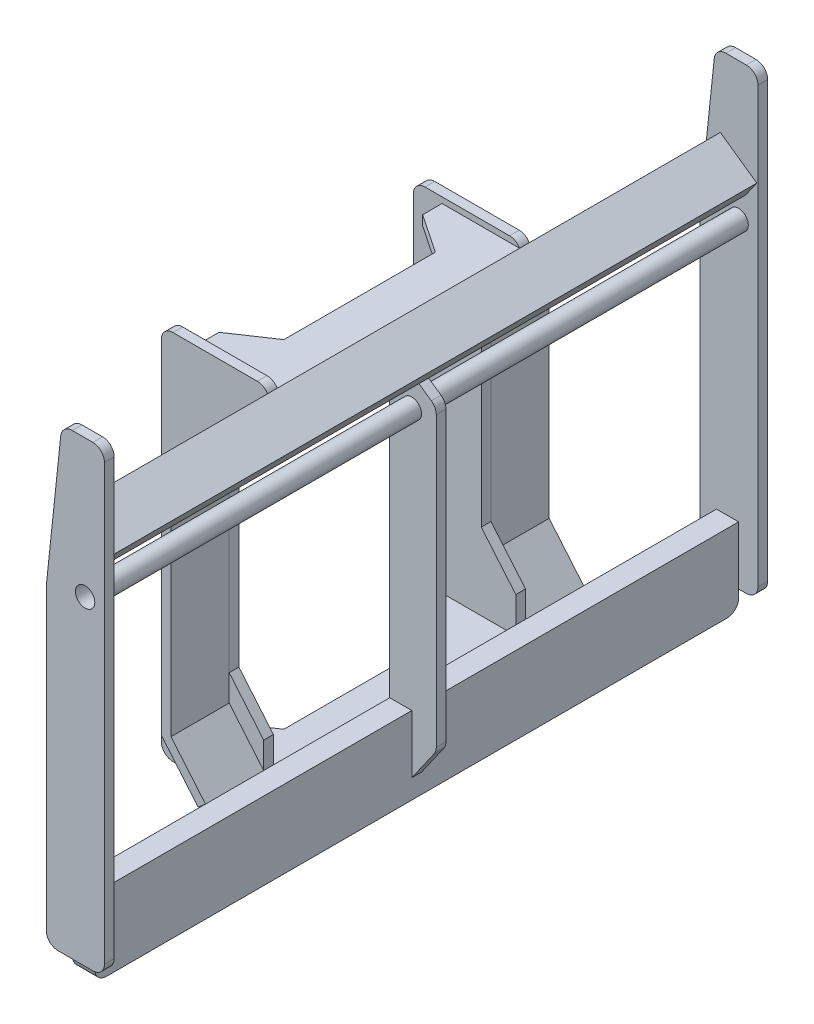
SolidWorks part; units mm, degrees
ref_plane "Front Plane" through (0, 0, 0) normal (0, 0, 1) x (1, 0, 0)
ref_plane "Top Plane" through (0, 0, 0) normal (0, 1, 0) x (1, 0, 0)
ref_plane "Right Plane" through (0, 0, 0) normal (1, 0, 0) x (0, 0, -1)
sketch "Sketch1" plane through (0, 0, 0) normal (0, 0, 1) x (1, 0, 0)
  line L0 (0, 1180) -> (0, 0)
  line L1 (0, 0) -> (-150, 0)
  line L2 (-150, 0) -> (-150, 800)
  line L3 (-150, 800) -> (-110, 1180)
  line L4 (-110, 1180) -> (0, 1180)
  dimension "D1" = 1180
  dimension "D2" = 110
  dimension "D3" = 150
  dimension "D4" = 800
extrude "Boss-Extrude1" add sketch "Sketch1" along normal blind 25 from offset 830
extrude "Boss-Extrude2" add sketch "Sketch1<2>" against normal blind 25 from offset 830 separate body offset against normal yes
sketch "Sketch1<2>" plane through (0, 0, 0) normal (0, 0, 1) x (1, 0, 0) same geometry as "Sketch1"
sketch "Sketch2" plane through (0, 0, -830) normal (0, 0, 1) x (1, 0, 0)
  line L0 (-3, 930) -> (-97.2025, 995.9613)
  line L1 (-107, 150) -> (-50, 150)
  line L2 (-107, 150) -> (-107, -50)
  line L3 (-107, -50) -> (-50, -50)
  line L4 (-50, 150) -> (-50, -50)
  line L5 (-3, 930) -> (-31.6788, 889.0424)
  line L6 (-97.2025, 995.9613) -> (-125.8813, 955.0037)
  line L7 (-31.6788, 889.0424) -> (-125.8813, 955.0037)
  line L8 (-3, 930) -> (-125.8813, 955.0037) construction
  line L9 (-97.2025, 995.9613) -> (-31.6788, 889.0424) construction
  line L10 (0, 0) -> (0, 1180) construction
  line L11 (0, 1180) -> (-110, 1180) construction
  line L12 (-150, 0) -> (0, 0) construction
  point P4 (-59.316, 962.2235)
  point P5 (-64.4407, 942.5018)
  dimension "D1" = 55
  dimension "D2" = 50
  dimension "D3" = 115
  dimension "D4" = 250
  dimension "D5" = 57
  dimension "D6" = 50
  dimension "D7" = 150
  dimension "D8" = 200
  dimension "D9" = 3
extrude "Boss-Extrude3" add sketch "Sketch2" along normal up to surface (1660 mm away) up to face at (-82, 632, 830)
sketch "Sketch3" plane through (0, 0, 0) normal (0, 0, 1) x (1, 0, 0)
  line L0 (-107, 941.733) -> (-13.7424, 876.4333)
  line L1 (-13.7424, 876.4333) -> (13, 857.7081)
  line L2 (13, 857.7081) -> (13, 89.9733)
  line L3 (13, 89.9733) -> (-50, 0)
  line L4 (-50, 0) -> (-50, 150) construction
  line L5 (-50, 0) -> (-50, 150)
  line L6 (-50, 150) -> (-107, 150)
  line L7 (-107, 150) -> (-107, 941.733)
  line L8 (-50, 0) -> (0, 0) construction
  line L9 (-125.8813, 955.0037) -> (-31.6788, 889.0424) construction
  dimension "D1" = 120
  dimension "D2" = 150
  dimension "D3" = 55
  dimension "D4" = 0
extrude "Boss-Extrude4" add sketch "Sketch3" along normal mid plane 25
sketch "Sketch4" plane through (0, 0, 855) normal (0, 0, 1) x (1, 0, 0)
  line L0 (0, 0) -> (0, 1180) construction
  line L1 (0, 1180) -> (-110, 1180) construction
  circle A0 centre (-50, 825) radius 25
  dimension "D1" = 50
  dimension "D2" = 50
  dimension "D3" = 355
extrude "Cut-Extrude1" cut sketch "Sketch4" against normal through all
sketch "Sketch5" plane through (0, 0, 855) normal (0, 0, 1) x (1, 0, 0)
  circle A0 centre (-50, 825) radius 25 construction
  circle A1 centre (-50, 825) radius 25
  circle A2 centre (-50, 825) radius 25.01
  dimension "D1" = 0.01
extrude "Boss-Extrude5" add sketch "Sketch5" against normal up to surface (1710 mm away) up to face at (-25, 825, -855)
sketch "Sketch7" plane through (0, 0, -12.5) normal (0, 0, -1) x (-1, 0, 0)
  line L0 (125.8813, 955.0037) -> (97.2025, 995.9613) construction
  line L1 (31.6788, 889.0424) -> (125.8813, 955.0037) construction
  line L2 (125.8813, 955.0037) -> (97.2025, 995.9613)
  line L3 (78.7801, 922.023) -> (125.8813, 955.0037)
  line L4 (107, 150) -> (50, 150) construction
  line L5 (107, 150) -> (50, 150)
  line L6 (97.2025, 995.9613) -> (97.2025, 1010.9613)
  line L7 (371, 1010.9613) -> (371, 52.9613)
  line L8 (371, 52.9613) -> (107, 52.9613)
  line L10 (107, 52.9613) -> (107, 150)
  line L11 (50, 150) -> (196, 323.996)
  line L12 (196, 323.996) -> (196, 816.4777)
  line L13 (196, 816.4777) -> (78.7801, 922.023)
  line L14 (97.2025, 1010.9613) -> (371, 1010.9613)
  line L17 (107, 941.733) -> (107, 150) construction
  point P1 (0, 0)
  point P5 (0, 0)
  line M15 (107, 941.733) -> (-13, 857.7081)
  line M20 (107, 150) -> (107, 941.733)
  dimension "D1" = 77
  dimension "D2" = 50
  dimension "D3" = 958
  dimension "D4" = 89
  dimension "D5" = 15
  dimension "D6" = 175
extrude "Boss-Extrude6" add sketch "Sketch7" along normal blind 25 from offset 300 contours L14 L6 L2 L3 L13 L12 L11 L10 L8 L7 M15 M20 region at (-262.432, 523.4884, -12.5)
sketch "Sketch8" plane through (0, 0, -337.5) normal (0, 0, -1) x (-1, 0, 0)
  line L0 (107, 150) -> (196, 256.0661)
  line L1 (196, 256.0661) -> (196, 844.4935)
  line L2 (196, 844.4935) -> (107, 919.1733)
  line L3 (107, 896.6137) -> (107, 941.733) construction
  line L4 (196, 323.996) -> (196, 816.4777) construction
  dimension "D1" = 130
  dimension "D2" = 140
  dimension "D3" = 0
extrude "Extrude-Thin1" add sketch "Sketch8" along normal blind 150 separate body thin thin type one direction wall 25
sketch "Sketch9" plane through (389.8143, 327.0931, 0) normal (0.766, 0.6428, 0) x (0, 0, -1)
  line L4 (337.5, 797.9059) -> (337.5, 772.9059)
  line L5 (337.5, 772.9059) -> (487.5, 772.9059)
  line L6 (487.5, 772.9059) -> (487.5, 797.9059)
  line L7 (487.5, 797.9059) -> (337.5, 797.9059)
  line L8 (337.5, 797.9059) -> (337.5, 772.9059)
  line L9 (337.5, 772.9059) -> (487.5, 772.9059)
  line L10 (487.5, 772.9059) -> (487.5, 797.9059)
  line L11 (487.5, 797.9059) -> (337.5, 797.9059)
  dimension "D1" = 0
extrude "Boss-Extrude7" add sketch "Sketch9" along normal up to next separate body
mirror "Mirror4" about plane through (0, 0, 0) normal (0, 0, 1) of bodies 108 109 107
ref_plane "Plane1" through (0, 995.9613, 0) normal (0, 1, 0) x (1, 0, 0)
sketch "Sketch11" plane through (0, 995.9613, 0) normal (0, 1, 0) x (1, 0, 0)
  line L0 (-297.2025, 312.5) -> (-97.2025, 312.5)
  line L1 (-97.2025, 312.5) -> (-371, 312.5) construction
  line L2 (-97.2025, 312.5) -> (-97.2025, -312.5)
  line L3 (-97.2025, -312.5) -> (-297.2025, -312.5)
  line L4 (-97.2025, -312.5) -> (-371, -312.5) construction
  line L5 (-297.2025, -312.5) -> (-297.2025, -262.5)
  line L6 (-297.2025, -262.5) -> (-197.2025, -195.3178)
  line L7 (-197.2025, -195.3178) -> (-197.2025, 195.3178)
  line L8 (-197.2025, 195.3178) -> (-297.2025, 262.5)
  line L9 (-297.2025, 262.5) -> (-297.2025, 312.5)
  line L10 (0, 0) -> (-362.6622, 0) construction
  dimension "D1" = 100
  dimension "D2" = 50
  dimension "D3" = 200
  dimension "D4" = 200
extrude "Boss-Extrude8" add sketch "Sketch11" against normal blind 25
pattern_linear "LPattern1" count 2 spacing 870 along (0, -1, 0) of "Boss-Extrude8"
fillet "Fillet1" radius 30 18 edges at (0, 1180, 842.5) (-110, 1180, 842.5) (-150, 0, 842.5) (0, 0, 842.5) (-78.5, -50, 830) (13, 857.7081, 0) (13, 89.9733, 0) (-78.5, -50, -830) (0, 0, -842.5) (0, 1180, -842.5) (-110, 1180, -842.5) (-150, 0, -842.5) (-371, 52.9613, -325) (-371, 1010.9613, -325) (-97.2025, 1010.9613, -325) (-97.2025, 1010.9613, 325) (-371, 1010.9613, 325) (-371, 52.9613, 325)
